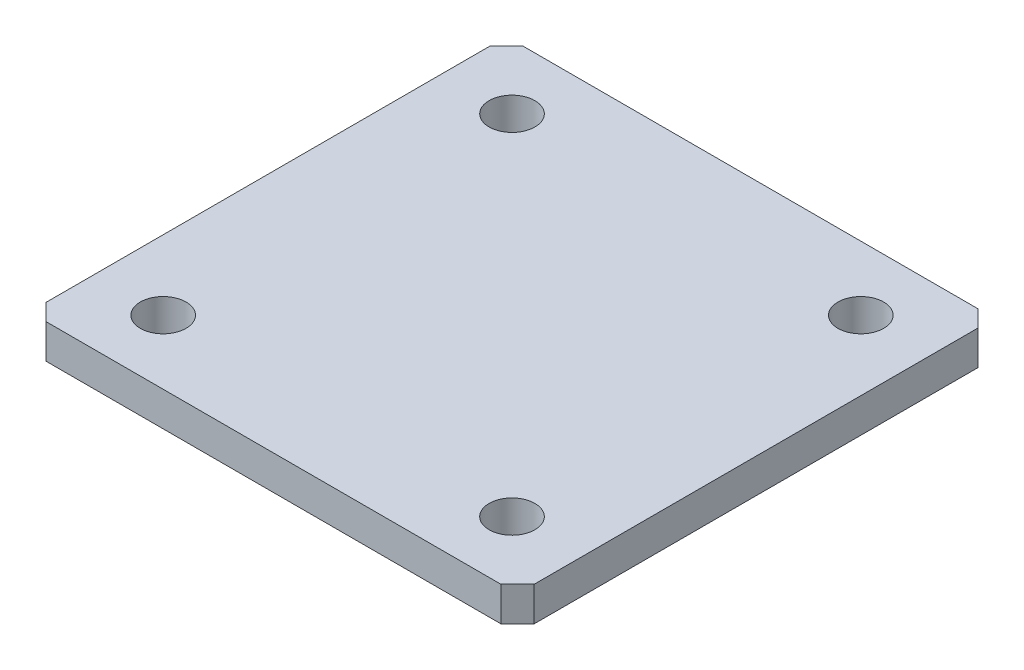
SolidWorks part; units mm, degrees
ref_plane "前视基准面" through (0, 0, 0) normal (0, 0, 1) x (1, 0, 0)
ref_plane "上视基准面" through (0, 0, 0) normal (0, 1, 0) x (1, 0, 0)
ref_plane "右视基准面" through (0, 0, 0) normal (1, 0, 0) x (0, 0, -1)
other "Configuration Table"
sketch "草图1" plane through (0, 0, 0) normal (0, 1, 0) x (1, 0, 0)
  line L0 (-19.8873, -20.8574) -> (19.8873, -20.8574)
  line L1 (19.8873, -20.8574) -> (21.3424, -19.4022)
  line L2 (21.3424, -19.4022) -> (21.3424, 19.4022)
  line L3 (21.3424, 19.4022) -> (19.8873, 20.8574)
  line L4 (19.8873, 20.8574) -> (-19.8873, 20.8574)
  line L5 (-19.8873, 20.8574) -> (-21.3424, 19.4022)
  line L6 (-21.3424, 19.4022) -> (-21.3424, -19.4022)
  line L7 (-21.3424, -19.4022) -> (-19.8873, -20.8574)
  line L8 (0, 0) -> (30.3044, 0) construction
  line L9 (0, 0) -> (0, -9.0996) construction
  circle A0 centre (15.25, 15.25) radius 2
  circle A1 centre (-15.25, 15.25) radius 2
  circle A2 centre (15.25, -15.25) radius 2
  circle A3 centre (-15.25, -15.25) radius 2
  dimension "D3" = 4
  dimension "D1" = 15.25
  dimension "D2" = 15.25
extrude "凸台-拉伸1" add sketch "草图1" along normal blind 3
